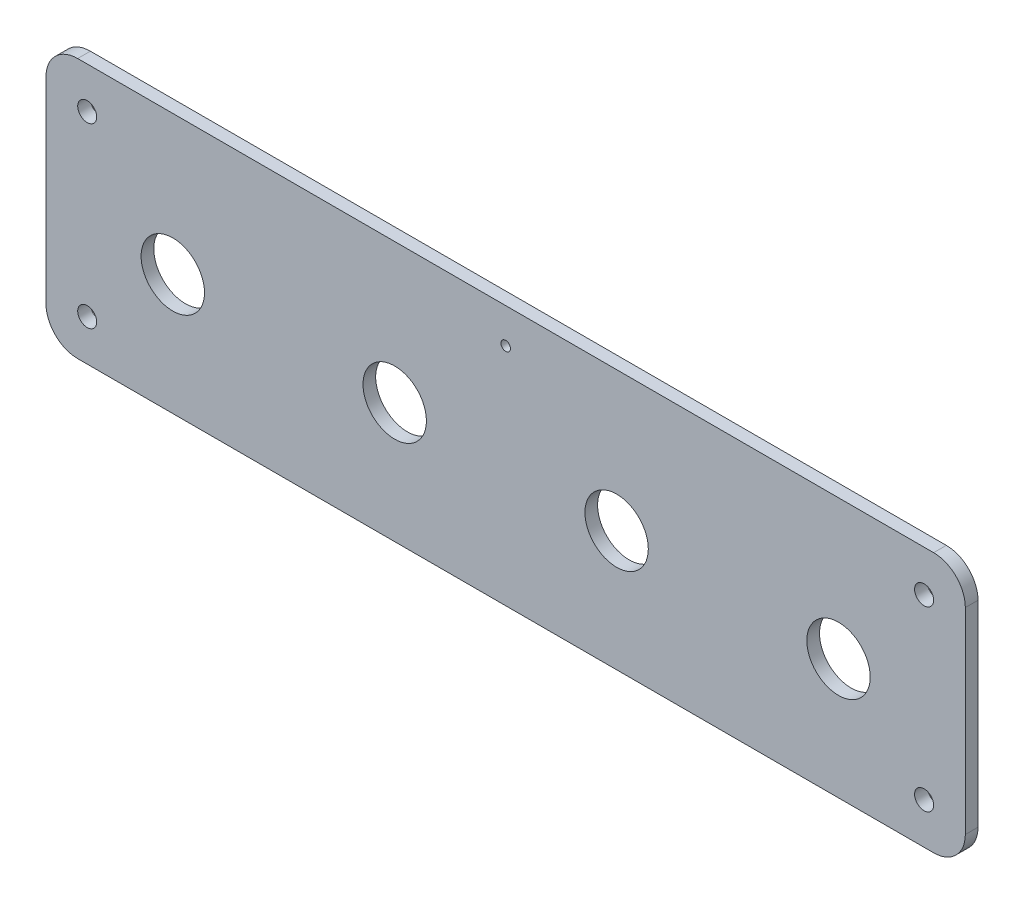
SolidWorks part; units mm, degrees
ref_plane "Alzado" through (0, 0, 0) normal (0, 0, 1) x (1, 0, 0)
ref_plane "Planta" through (0, 0, 0) normal (0, 1, 0) x (1, 0, 0)
ref_plane "Vista lateral" through (0, 0, 0) normal (1, 0, 0) x (0, 0, -1)
sketch "Croquis1" plane through (0, 0, 0) normal (0, 0, 1) x (1, 0, 0)
  line L1 (-67.5, -20.5) -> (67.5, -20.5)
  line L2 (-72.5, -15.5) -> (-72.5, 15.5)
  line L3 (-67.5, 20.5) -> (67.5, 20.5)
  line L4 (72.5, -15.5) -> (72.5, 15.5)
  line L5 (-72.5, -20.5) -> (72.5, 20.5) construction
  line L6 (-72.5, 20.5) -> (72.5, -20.5) construction
  line L7 (-70, -18) -> (70, -18) construction
  line L8 (-70, -18) -> (-70, 18) construction
  line L9 (-70, 18) -> (70, 18) construction
  line L10 (70, -18) -> (70, 18) construction
  line L11 (-70, -18) -> (70, 18) construction
  line L12 (-70, 18) -> (70, -18) construction
  arc A0 (67.5, 20.5) -> (72.5, 15.5) centre (67.5, 15.5) cw
  arc A1 (72.5, -15.5) -> (67.5, -20.5) centre (67.5, -15.5) cw
  arc A2 (-67.5, -20.5) -> (-72.5, -15.5) centre (-67.5, -15.5) cw
  arc A3 (-72.5, 15.5) -> (-67.5, 20.5) centre (-67.5, 15.5) cw
  circle A4 centre (-52.5, -1.5) radius 5
  circle A5 centre (-17.5, -1.5) radius 5
  circle A6 centre (17.5, -1.5) radius 5
  circle A7 centre (52.5, -1.5) radius 5
  circle A8 centre (0, 15) radius 0.75
  circle A9 centre (-66, 14) radius 1.5
  circle A10 centre (-66, -14) radius 1.5
  circle A11 centre (66, -14) radius 1.5
  circle A12 centre (66, 14) radius 1.5
  point P0 (0, 0)
  point P31 (0, 0)
  point P41 (0, 0)
  point P42 (0, 0)
  point P43 (0, 0)
  point P44 (0, 0)
  dimension "D3" = 5
  dimension "D5" = 36
  dimension "D6" = 10
  dimension "D8" = 35
  dimension "D9" = 35
  dimension "D12" = 1.5
  dimension "D13" = 5.5
  dimension "D14" = 3
  dimension "D15" = 4
  dimension "D16" = 4
  dimension "D17" = 4
  dimension "D18" = 4
  dimension "D1" = 145
  dimension "D2" = 41
  dimension "D4" = 140
  dimension "D7" = 35
  dimension "D10" = 16.5
  dimension "D11" = 17.5
extrude "Saliente-Extruir1" add sketch "Croquis1" against normal blind 2
